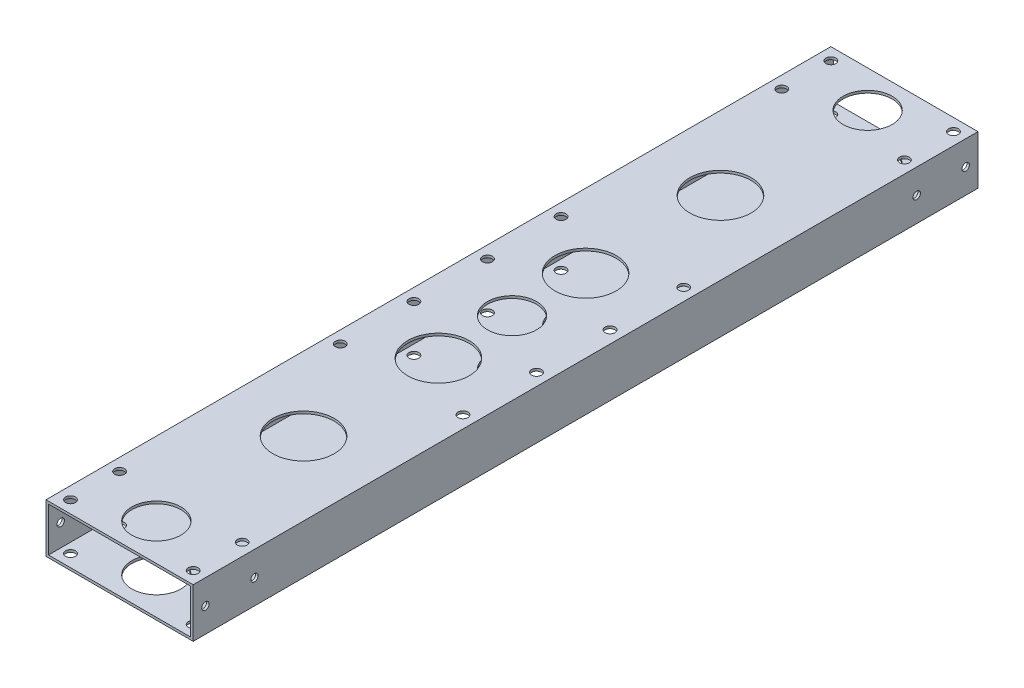
SolidWorks part; units mm, degrees
ref_plane "前视基准面" through (0, 0, 0) normal (0, 0, 1) x (1, 0, 0)
ref_plane "上视基准面" through (0, 0, 0) normal (0, 1, 0) x (1, 0, 0)
ref_plane "右视基准面" through (0, 0, 0) normal (1, 0, 0) x (0, 0, -1)
sketch "草图1" plane through (0, 0, 0) normal (0, 0, 1) x (1, 0, 0)
  line L1 (0, 0) -> (60, 0)
  line L2 (0, 0) -> (0, 20)
  line L3 (0, 20) -> (60, 20)
  line L4 (60, 0) -> (60, 20)
  dimension "D1" = 60
  dimension "D2" = 20
extrude "拉伸-薄壁1" add sketch "草图1" along normal blind 320 thin thin type one direction reverse wall 1
sketch "草图2" plane through (0, 20, 0) normal (0, 1, 0) x (1, 0, 0)
  line L0 (0, -160) -> (60, -160) construction
  line L1 (0, -320) -> (0, 0) construction
  line L2 (60, -320) -> (60, 0) construction
  line L3 (5, -145) -> (5, -175) construction
  line L4 (30, 0) -> (30, -320) construction
  line L5 (60, 0) -> (0, 0) construction
  line L6 (60, -320) -> (0, -320) construction
  line L7 (55, -145) -> (55, -175) construction
  line L8 (5, -315) -> (55, -295) construction
  line L10 (5, -25) -> (55, -25) construction
  line L11 (5, -25) -> (5, -5) construction
  line L12 (5, -5) -> (55, -5) construction
  line L13 (55, -25) -> (55, -5) construction
  line L14 (5, -25) -> (55, -5) construction
  line L15 (5, -5) -> (55, -25) construction
  line L16 (5, -295) -> (55, -315) construction
  line L17 (55, -295) -> (55, -315) construction
  line L18 (5, -315) -> (55, -315) construction
  line L19 (5, -295) -> (5, -315) construction
  line L20 (5, -295) -> (55, -295) construction
  circle A0 centre (5, -145) radius 2
  circle A1 centre (5, -175) radius 2
  circle A2 centre (55, -175) radius 2
  circle A3 centre (55, -145) radius 2
  circle A4 centre (5, -115) radius 2
  circle A5 centre (5, -205) radius 2
  circle A6 centre (55, -205) radius 2
  circle A7 centre (55, -115) radius 2
  circle A8 centre (5, -5) radius 2
  circle A9 centre (55, -5) radius 2
  circle A10 centre (55, -25) radius 2
  circle A11 centre (5, -25) radius 2
  circle A12 centre (5, -295) radius 2
  circle A13 centre (55, -295) radius 2
  circle A14 centre (55, -315) radius 2
  circle A15 centre (5, -315) radius 2
  point P14 (5, -160)
  point P23 (30, -15)
  point P46 (30, -305)
  dimension "D3" = 4
  dimension "D4" = 4
  dimension "D6" = 5
  dimension "D9" = 4
  dimension "D1" = 30
  dimension "D2" = 5
  dimension "D5" = 90
  dimension "D7" = 5
  dimension "D8" = 20
extrude "切除-拉伸1" cut sketch "草图2" against normal through all
sketch "草图4" plane through (60, 0, 0) normal (1, 0, 0) x (0, 0, -1)
  line L0 (-320, 10) -> (0, 10) construction
  line L1 (-320, 0) -> (-320, 20) construction
  line L2 (0, 0) -> (0, 20) construction
  line L3 (-160, 20) -> (-160, 0) construction
  line L4 (-320, 20) -> (0, 20) construction
  line L5 (-320, 0) -> (0, 0) construction
  circle A0 centre (-315, 10) radius 1.5
  circle A1 centre (-295, 10) radius 1.5
  circle A2 centre (-25, 10) radius 1.5
  circle A3 centre (-5, 10) radius 1.5
  dimension "D1" = 5
  dimension "D3" = 3
  dimension "D2" = 20
extrude "切除-拉伸2" cut sketch "草图4" against normal through all
sketch "草图5" plane through (0, 20, 0) normal (0, 1, 0) x (1, 0, 0)
  line L0 (0, -160) -> (60, -160) construction
  line L1 (0, -320) -> (0, 0) construction
  line L2 (60, -320) -> (60, 0) construction
  circle A0 centre (30, -160) radius 10
  circle A1 centre (30, -130) radius 12.5
  circle A2 centre (30, -190) radius 12.5
  circle A3 centre (30, -75) radius 12.5
  circle A4 centre (30, -15) radius 10
  circle A5 centre (30, -305) radius 10
  circle A6 centre (30, -245) radius 12.5
  dimension "D1" = 20
  dimension "D2" = 25
  dimension "D4" = 85
  dimension "D5" = 25
  dimension "D6" = 145
  dimension "D7" = 20
  dimension "D3" = 30
extrude "切除-拉伸3" cut sketch "草图5" against normal through all
